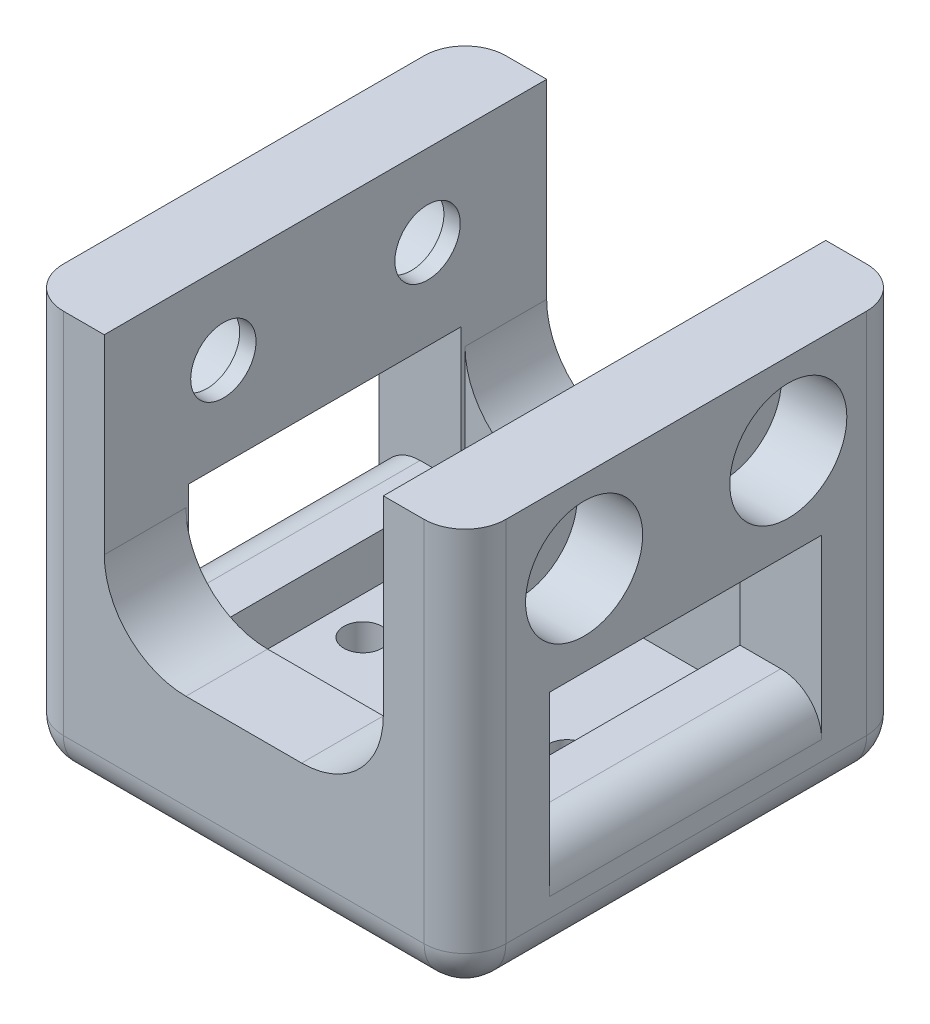
SolidWorks part; units mm, degrees
ref_plane "Front Plane" through (0, 0, 0) normal (0, 0, 1) x (1, 0, 0)
ref_plane "Top Plane" through (0, 0, 0) normal (0, 1, 0) x (1, 0, 0)
ref_plane "Right Plane" through (0, 0, 0) normal (1, 0, 0) x (0, 0, -1)
sketch "Sketch1" plane through (0, 0, 0) normal (0, 1, 0) x (1, 0, 0)
  line L0 (0, 9.525) -> (0, -9.525) construction
  line L5 (9.525, 0) -> (-9.525, 0) construction
  line L9 (-13.0175, -13.0175) -> (13.0175, -13.0175)
  line L10 (-13.0175, -13.0175) -> (-13.0175, 13.0175)
  line L11 (-13.0175, 13.0175) -> (13.0175, 13.0175)
  line L12 (13.0175, -13.0175) -> (13.0175, 13.0175)
  circle A0 centre (0, 9.525) radius 1.778
  circle A1 centre (-9.525, 0) radius 1.778
  circle A2 centre (9.525, 0) radius 1.778
  circle A3 centre (0, -9.525) radius 1.778
  point P4 (-13.0175, 0)
  point P6 (0, -13.0175)
  point P11 (0, 0)
  point P12 (0, 0)
  dimension "D5" = 3.556
  dimension "D1" = 26.035
  dimension "D2" = 26.035
  dimension "D3" = 19.05
  dimension "D4" = 19.05
extrude "Boss-Extrude1" add sketch "Sketch1" along normal blind 5.08
sketch "Sketch9" plane through (0, 0, 0) normal (0, -1, 0) x (1, 0, 0)
  line L22 (20.6375, -20.6375) -> (20.6375, 20.6375)
  line L23 (-13.0175, -13.0175) -> (13.0175, -13.0175)
  line L24 (-13.0175, -13.0175) -> (-13.0175, 13.0175)
  line L25 (-13.0175, 13.0175) -> (13.0175, 13.0175)
  line L26 (13.0175, -13.0175) -> (13.0175, 13.0175)
  line L27 (-20.6375, 20.6375) -> (20.6375, 20.6375)
  line L28 (-20.6375, -20.6375) -> (-20.6375, 20.6375)
  line L29 (-20.6375, -20.6375) -> (20.6375, -20.6375)
  dimension "D1" = 7.62
extrude "Boss-Extrude7" add sketch "Sketch9" against normal blind 38.1
sketch "Sketch10" plane through (0, 0, 20.6375) normal (0, 0, 1) x (1, 0, 0)
  line L0 (-13.0175, 20.32) -> (-13.0175, 38.1)
  line L1 (20.6375, 38.1) -> (-20.6375, 38.1) construction
  line L2 (-13.0175, 38.1) -> (13.0175, 38.1)
  line L3 (13.0175, 38.1) -> (13.0175, 20.32)
  line L4 (5.3975, 12.7) -> (-5.3975, 12.7)
  arc A0 (13.0175, 20.32) -> (5.3975, 12.7) centre (5.3975, 20.32) cw
  arc A1 (-13.0175, 20.32) -> (-5.3975, 12.7) centre (-5.3975, 20.32) ccw
  point P10 (0, 38.1)
  point P11 (0, 38.1)
  dimension "D1" = 7.62
  dimension "D2" = 26.035
  dimension "D3" = 25.4
extrude "Cut-Extrude4" cut sketch "Sketch10" against normal through all
sketch "Sketch11" plane through (-20.6375, 0, 0) normal (-1, 0, 0) x (0, 0, 1)
  line L0 (-9.525, 30.48) -> (9.525, 30.48) construction
  line L1 (20.6375, 38.1) -> (-20.6375, 38.1) construction
  circle A0 centre (-9.525, 30.48) radius 3.048
  circle A1 centre (9.525, 30.48) radius 3.048
  point P4 (0, 30.48)
  point P7 (0, 38.1)
  dimension "D1" = 6.096
  dimension "D2" = 19.05
  dimension "D3" = 17.78
extrude "Cut-Extrude5" cut sketch "Sketch11" against normal through all
fillet "Fillet1" radius 3.81 4 edges at (20.6375, 19.05, -20.6375) (20.6375, 19.05, 20.6375) (-20.6375, 19.05, -20.6375) (-20.6375, 19.05, 20.6375)
fillet "Fillet2" radius 3.81 8 edges at (19.5216, 0, 19.5216) (20.6375, 0, 0) (19.5216, 0, -19.5216) (0, 0, -20.6375) (-19.5216, 0, -19.5216) (-20.6375, 0, 0) (-19.5216, 0, 19.5216) (0, 0, 20.6375)
sketch "Sketch12" plane through (-20.6375, 0, 0) normal (-1, 0, 0) x (0, 0, 1)
  circle A0 centre (-9.525, 30.48) radius 5.461
  circle A1 centre (9.525, 30.48) radius 5.461
  circle M2 centre (-9.525, 30.48) radius 3.048
  circle M3 centre (9.525, 30.48) radius 3.048
extrude "Cut-Extrude6" cut sketch "Sketch12" against normal blind 6.096 contours A0 M2 | A1 M3 region at (-20.6375, 30.48, -14.8315) region at (-20.6375, 30.48, 4.2185)
extrude "Cut-Extrude7" cut sketch "Sketch12<3>" along normal blind 6.096 from surface starting at face at (20.6375, 30.48, -6.477)
sketch "Sketch12<3>" plane through (-20.6375, 0, 0) normal (-1, 0, 0) x (0, 0, 1) same geometry as "Sketch12"
sketch "Sketch13" plane through (-20.6375, 0, 0) normal (-1, 0, 0) x (0, 0, 1)
  line L1 (-12.6365, 22.098) -> (12.7635, 22.098)
  line L2 (-12.6365, 22.098) -> (-12.6365, 9.398)
  line L3 (-12.6365, 9.398) -> (12.7635, 9.398)
  line L4 (12.7635, 22.098) -> (12.7635, 9.398)
  line L7 (16.8275, 38.1) -> (-16.8275, 38.1) construction
  point P4 (-12.6365, 15.748)
  point P6 (0.0635, 9.398)
  dimension "D1" = 25.4
  dimension "D2" = 12.7
  dimension "D3" = 20.701
  dimension "D4" = 22.352
extrude "Cut-Extrude8" cut sketch "Sketch13" against normal through all
fillet "Fillet3" radius 3.81 1 edges at (-20.6375, 9.398, 0.0635)
fillet "Fillet4" radius 3.81 1 edges at (20.6375, 9.398, 0.0635)
